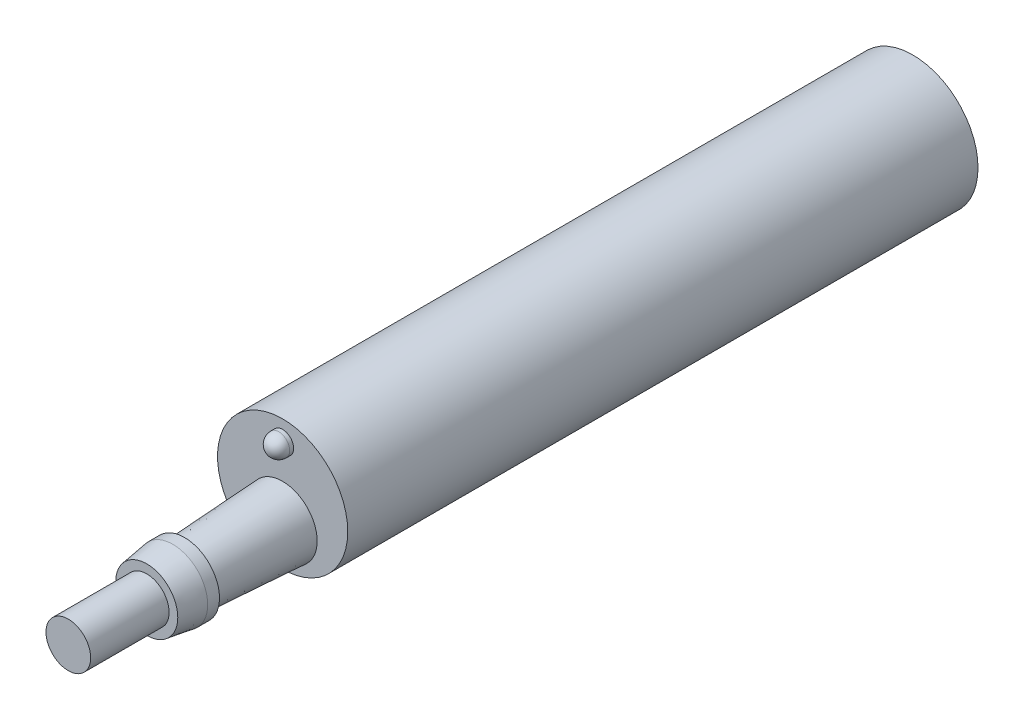
SolidWorks part; units mm, degrees
material "ABS"
ref_plane "Front Plane" through (0, 0, 0) normal (0, 0, 1) x (1, 0, 0)
ref_plane "Top Plane" through (0, 0, 0) normal (0, 1, 0) x (1, 0, 0)
ref_plane "Right Plane" through (0, 0, 0) normal (1, 0, 0) x (0, 0, -1)
sketch "Sketch1" plane through (0, 0, 0) normal (0, 0, 1) x (1, 0, 0)
  circle A0 centre (0, 0) radius 8.3
  dimension "D1" = 16.6
extrude "Boss-Extrude1" add sketch "Sketch1" along normal blind 80.34
sketch "Sketch2" plane through (0, 0, 80.34) normal (0, 0, 1) x (1, 0, 0)
  line L0 (0, 0) -> (0, 8.3) construction
  circle A0 centre (0, 0) radius 8.3 construction
  circle A1 centre (0, 5.73) radius 1.4
  dimension "D2" = 2.8
  dimension "D1" = 2.57
extrude "Boss-Extrude2" add sketch "Sketch2" along normal blind 0.5
dome "Dome1" faces to dome 1 distance 1.4 reverse direction no elliptical dome no face at (1.4, 5.73, 80.84) parameters "D1"=1.4
sketch "Sketch3" plane through (0, 0, 80.34) normal (0, 0, 1) x (1, 0, 0)
  line L0 (0, 0) -> (0, -8.3) construction
  circle A0 centre (0, 0) radius 8.3 construction
  circle A1 centre (0, -3) radius 4.4
  dimension "D1" = 8.8
  dimension "D2" = 3
extrude "Boss-Extrude3" add sketch "Sketch3" along normal blind 12.5 draft 3.2
sketch "Sketch4" plane through (0, 0, 92.84) normal (0, 0, 1) x (1, 0, 0)
  circle A0 centre (0, -3) radius 4.45
  dimension "D1" = 8.9
extrude "Boss-Extrude4" add sketch "Sketch4" along normal blind 1.5
sketch "Sketch5" plane through (0, 0, 94.34) normal (0, 0, 1) x (1, 0, 0)
  circle A0 centre (0, -3) radius 4.45
extrude "Boss-Extrude5" add sketch "Sketch5" along normal blind 3.32 draft 8.5
sketch "Sketch6" plane through (0, 0, 97.66) normal (0, 0, 1) x (1, 0, 0)
  circle A0 centre (0, -3) radius 2.85
  dimension "D1" = 5.7
extrude "Boss-Extrude6" add sketch "Sketch6" along normal blind 10
